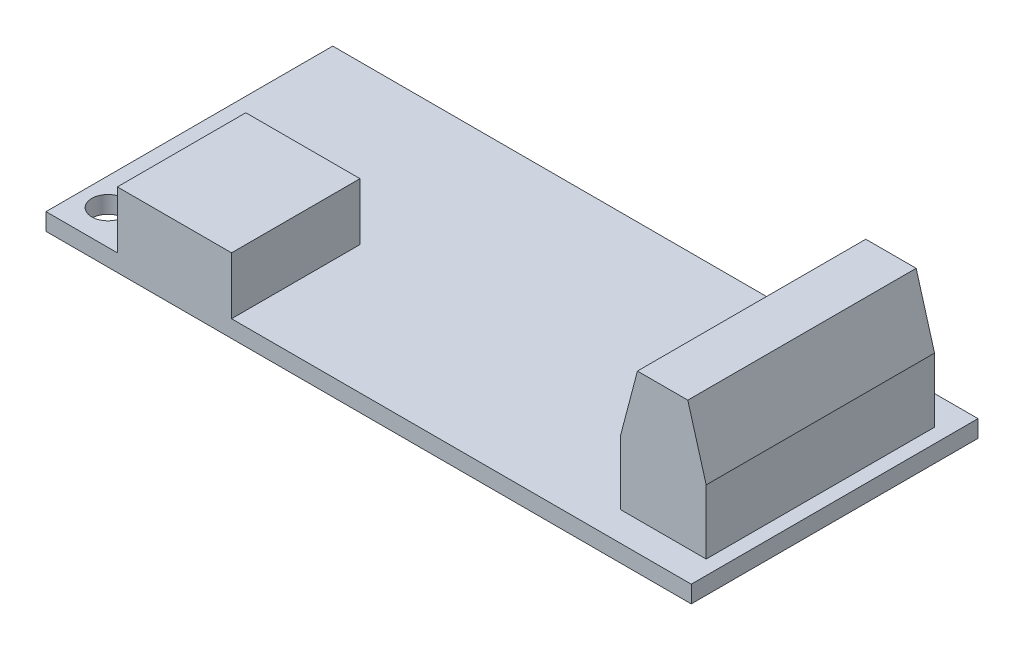
SolidWorks part; units mm, degrees
ref_plane "Front Plane" through (0, 0, 0) normal (0, 0, 1) x (1, 0, 0)
ref_plane "Top Plane" through (0, 0, 0) normal (0, 1, 0) x (1, 0, 0)
ref_plane "Right Plane" through (0, 0, 0) normal (1, 0, 0) x (0, 0, -1)
sketch "Sketch1" plane through (0, 0, 0) normal (0, 1, 0) x (1, 0, 0)
  line L1 (-22.605, 10.045) -> (22.605, 10.045)
  line L2 (-22.605, 10.045) -> (-22.605, -10.045)
  line L3 (-22.605, -10.045) -> (22.605, -10.045)
  line L4 (22.605, 10.045) -> (22.605, -10.045)
  line L5 (-22.605, 10.045) -> (22.605, -10.045) construction
  line L6 (-22.605, -10.045) -> (22.605, 10.045) construction
  circle A0 centre (11.835, 7.785) radius 1.13
  circle A1 centre (-20.675, -7.635) radius 1.13
  point P4 (0, 0)
  point P10 (0, 0)
  point P12 (5.8022, 1.5862)
  dimension "D3" = 2.26
  dimension "D4" = 2.26
  dimension "D1" = 45.21
  dimension "D2" = 20.09
  dimension "D5" = 1.93
  dimension "D6" = 32.51
  dimension "D7" = 15.42
  dimension "D8" = 17.68
extrude "Boss-Extrude1" add sketch "Sketch1" along normal blind 1.2
sketch "Sketch2" plane through (0, 1.2, 0) normal (0, 1, 0) x (1, 0, 0)
  line L0 (22.605, -10.045) -> (22.605, 10.045) construction
  line L1 (15.605, 8) -> (21.605, 8)
  line L2 (15.605, 8) -> (15.605, -8)
  line L3 (15.605, -8) -> (21.605, -8)
  line L4 (21.605, 8) -> (21.605, -8)
  line L5 (15.605, 8) -> (21.605, -8) construction
  line L6 (15.605, -8) -> (21.605, 8) construction
  point P4 (18.605, 0)
  point P5 (21.605, 0)
  point P8 (22.605, 0)
  dimension "D1" = 16
  dimension "D2" = 6
  dimension "D3" = 1
extrude "Boss-Extrude3" add sketch "Sketch2" along normal blind 9
sketch "Sketch4" plane through (0, 0, 8) normal (0, 0, 1) x (1, 0, 0)
  line L0 (15.605, 5.7) -> (16.7882, 10.2)
  line L1 (15.605, 10.2) -> (21.605, 10.2) construction
  line L2 (15.605, 10.2) -> (15.605, 1.2) construction
  line L3 (20.3174, 10.2) -> (21.605, 5.7)
  line L4 (21.605, 10.2) -> (21.605, 1.2) construction
  line L5 (20.3174, 10.2) -> (21.605, 10.2)
  line L6 (21.605, 10.2) -> (21.605, 5.7)
  line L7 (16.7882, 10.2) -> (15.605, 10.2)
  line L8 (15.605, 10.2) -> (15.605, 5.7)
extrude "Cut-Extrude1" cut sketch "Sketch4" against normal up to next
sketch "Sketch5" plane through (0, 1.2, 0) normal (0, 1, 0) x (1, 0, 0)
  line L0 (-22.605, 10.045) -> (-22.605, -10.045) construction
  line L1 (-17.605, -1.045) -> (-9.605, -1.045)
  line L2 (-17.605, -1.045) -> (-17.605, -10.045)
  line L3 (-17.605, -10.045) -> (-9.605, -10.045)
  line L4 (-9.605, -1.045) -> (-9.605, -10.045)
  line L5 (-17.605, -1.045) -> (-9.605, -10.045) construction
  line L6 (-17.605, -10.045) -> (-9.605, -1.045) construction
  point P4 (-13.605, -5.545)
  dimension "D1" = 8
  dimension "D2" = 9
  dimension "D3" = 5
extrude "Boss-Extrude5" add sketch "Sketch5" along normal blind 4
